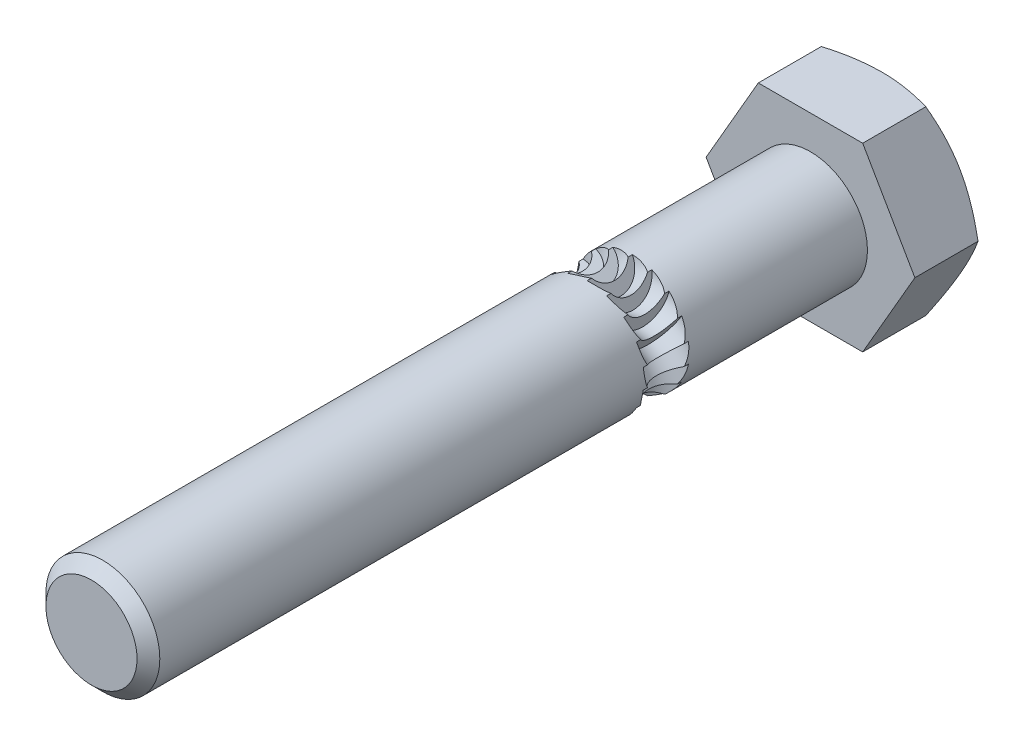
SolidWorks part; units mm, degrees
ref_plane "Front Plane" through (0, 0, 0) normal (0, 0, 1) x (1, 0, 0)
ref_plane "Top Plane" through (0, 0, 0) normal (0, 1, 0) x (1, 0, 0)
ref_plane "Right Plane" through (0, 0, 0) normal (1, 0, 0) x (0, 0, -1)
sketch "Sketch1" plane through (0, 0, 0) normal (0, 0, 1) x (1, 0, 0)
  circle A0 centre (0, 0) radius 4
  dimension "D1" = 8
extrude "Bolt Body" add sketch "Sketch1" along normal blind 50.5
ref_axis "Axis1" through (0, 0, -10.3812) along (0, 0, 1)
sketch "Sketch3" plane through (0, 0, 0) normal (0, 0, 1) x (1, 0, 0)
  line L1 (7.3323, 0) -> (3.6662, 6.35)
  line L2 (3.6662, 6.35) -> (-3.6662, 6.35)
  line L3 (-3.6662, 6.35) -> (-7.3323, 0)
  line L4 (-7.3323, 0) -> (-3.6662, -6.35)
  line L5 (-3.6662, -6.35) -> (3.6662, -6.35)
  line L6 (3.6662, -6.35) -> (7.3323, 0)
  circle A1 centre (0, 0) radius 6.35 construction
  dimension "D2" = 12.7
extrude "Bolt Head" add sketch "Sketch3" against normal blind 5
sketch "Sketch5" plane through (0, 0, 0) normal (0, 1, 0) x (1, 0, 0)
  line L1 (0, 10.3812) -> (0, -69.3803) construction
  line L2 (-3.6662, 0) -> (-7.3323, 0) construction
  circle A0 centre (-3.5, -14.1) radius 1.5875
  dimension "D1" = 14.1
  dimension "D3" = 3.175
  dimension "D2" = 3.5
extrude "Cut-Extrude2" cut sketch "Sketch5" along normal through all from offset 2
pattern_circular "CirPattern1" count 18 over 360 about axis through (0, 0, -10.3812) along (0, 0, 1) of "Cut-Extrude2"
chamfer "Chamfer1" distance 0.8 angle 45 1 edges at (4, 0, 50.5)
sketch "Sketch6" plane through (0, 0, -5) normal (0, 0, -1) x (-1, 0, 0)
  circle A0 centre (0, 0) radius 6.35
extrude "Cut-Extrude3" cut sketch "Sketch6" against normal blind 10 draft 60 flip side to cut
